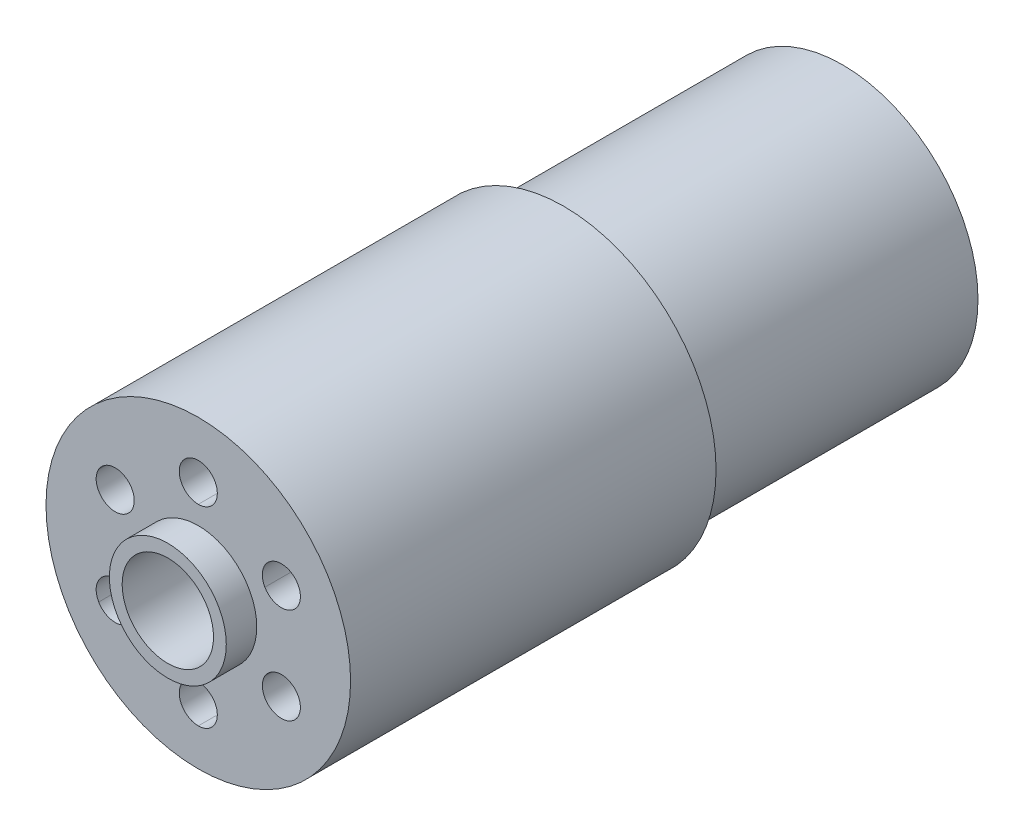
SolidWorks part; units mm, degrees
ref_plane "Front Plane" through (0, 0, 0) normal (0, 0, 1) x (1, 0, 0)
ref_plane "Top Plane" through (0, 0, 0) normal (0, 1, 0) x (1, 0, 0)
ref_plane "Right Plane" through (0, 0, 0) normal (1, 0, 0) x (0, 0, -1)
sketch "Sketch1" plane through (0, 0, 0) normal (0, 0, 1) x (1, 0, 0)
  circle A0 centre (0, 0) radius 25.4
  circle A8 centre (0, 0) radius 9.3953
  point P19 (0, 0)
  dimension "D1" = 50.8
  dimension "D2" = 16.0047
extrude "Boss-Extrude2" add sketch "Sketch1" along normal blind 107.442 contours A0
sketch "Sketch6" plane through (0, 0, 0) normal (0, 0, -1) x (-1, 0, 0)
  circle A0 centre (0, 0) radius 7.62
  circle A1 centre (-13.8581, 8.001) radius 3.175
  circle A2 centre (0, 16.002) radius 3.175
  circle A3 centre (13.8581, 8.001) radius 3.175
  circle A4 centre (13.8581, -8.001) radius 3.175
  circle A5 centre (0, -16.002) radius 3.175
  circle A6 centre (-13.8581, -8.001) radius 3.175
  point P18 (0, 0)
  dimension "D1" = 15.24
  dimension "D2" = 6.35
  dimension "D3" = 16.002
  dimension "D4" = 6
extrude "Cut-Extrude1" cut sketch "Sketch6" against normal blind 108.458
sketch "Sketch7" plane through (0, 0, 0) normal (0, 0, -1) x (-1, 0, 0)
  circle A0 centre (0, 0) radius 22.606
  circle A1 centre (0, 0) radius 25.4 construction
  circle A2 centre (0, 0) radius 25.4
  dimension "D1" = 2.794
extrude "Cut-Extrude2" cut sketch "Sketch7" against normal blind 46.482
sketch "Sketch8" plane through (0, 0, 107.442) normal (0, 0, 1) x (1, 0, 0)
  circle A0 centre (0, 0) radius 7.62
  circle A1 centre (0, 0) radius 9.75
  dimension "D1" = 19.5
  dimension "D2" = 15.24
extrude "Boss-Extrude7" add sketch "Sketch8" along normal blind 5.08
sketch "Sketch9" plane through (0, 0, 0) normal (0, 0, -1) x (-1, 0, 0)
  circle A0 centre (0, 0) radius 7.62
  circle A1 centre (0, 0) radius 9.75
  dimension "D1" = 19.5
  dimension "D2" = 15.24
extrude "Boss-Extrude8" add sketch "Sketch9" along normal blind 5.08
sketch "Sketch10" plane through (0, 0, 0) normal (0, 0, -1) x (-1, 0, 0)
  circle A0 centre (0, 16.002) radius 3.175 construction
  circle A1 centre (0, -16.002) radius 3.175 construction
  circle A2 centre (0, 0) radius 19.177 construction
  circle A3 centre (-13.8581, 8.001) radius 3.175 construction
  circle A4 centre (-13.8581, -8.001) radius 3.175 construction
  circle A5 centre (13.8581, -8.001) radius 3.175 construction
  circle A6 centre (0, 0) radius 12.827 construction
  point P0 (0, 19.177)
  point P1 (0, -19.177)
  point P9 (-16.6078, 9.5885)
  point P10 (-16.6078, -9.5885)
  point P13 (16.6078, -9.5885)
  point P16 (16.6078, 9.5885)
  point P20 (0, 12.827)
  point P21 (-10.9777, 6.6349)
  point P22 (-10.9777, -6.6349)
  point P23 (11.1085, -6.4135)
  point P24 (11.1085, 6.4135)
  point P25 (0, -12.827)
sketch "Sketch11" plane through (0, 0, 107.442) normal (0, 0, 1) x (1, 0, 0)
  point P0 (10.9777, 6.6349)
  point P2 (10.9777, -6.6349)
  point P4 (0, -12.827)
  point P6 (-11.1085, -6.4135)
  point P8 (-11.1085, 6.4135)
  point P10 (0, 12.827)
ref_plane "Plane1" through (0, 0, 0) normal (-1, 0, 0) x (0, 0, 1)
ref_plane "Plane3" through (0, 0, 0) normal (-0.5, -0.866, 0) x (-0.866, 0.5, 0)
ref_plane "Plane6" through (0, 0, 0) normal (0.5, -0.866, 0) x (-0.866, -0.5, 0)
split line "Split Line1"
split line "Split Line2"
split line "Split Line3"
ref_axis "Axis1" through (0, 0, 112.522) along (0, 0, -1)
